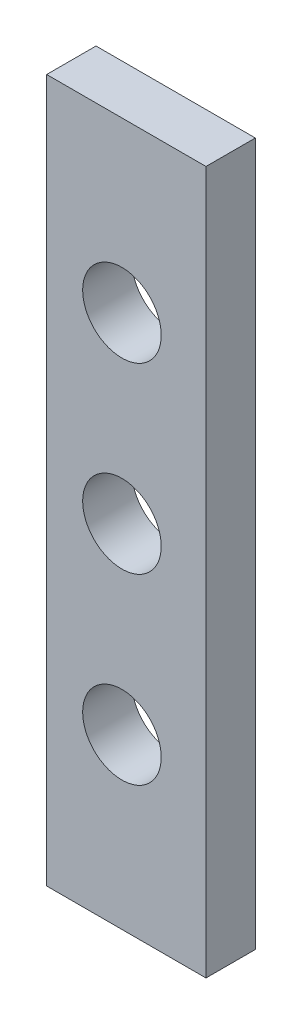
SolidWorks part; units mm, degrees
ref_plane "前视基准面" through (0, 0, 0) normal (0, 0, 1) x (1, 0, 0)
ref_plane "上视基准面" through (0, 0, 0) normal (0, 1, 0) x (1, 0, 0)
ref_plane "右视基准面" through (0, 0, 0) normal (1, 0, 0) x (0, 0, -1)
sketch "草图1" plane through (0, 0, 0) normal (0, 0, 1) x (1, 0, 0)
  line L6 (-130, -105) -> (-121.2816, -105)
  line L7 (-130, -105) -> (-130, -66.5374)
  line L8 (-130, -66.5374) -> (-121.2816, -66.5374)
  line L9 (-121.2816, -105) -> (-121.2816, -66.5374)
extrude "凸台-拉伸1" add sketch "草图1" along normal blind 2.7
hole_wizard "打孔尺寸(%根据十字)槽沉头木螺钉的类型1" positions "草图2" profile "草图3" countersink size "M4" standard "GB"
sketch "草图2" plane through (40.4914, -131.0101, 7) normal (0, 0, 1) x (0, 1, 0)
  point P0 (35.2414, 166.373)
  point P3 (45.2414, 166.373)
  point P6 (55.2414, 166.373)
  point P9 (206.7788, 166.373)
  point P12 (216.7788, 166.373)
  point P15 (226.7788, 166.373)
sketch "草图3" plane through (-125.8816, -95.7687, 7) normal (1, 0, 0) x (0, -1, 0)
  line L0 (0, 0) -> (0, 20.2919)
  line L1 (0, 20.2919) -> (2.15, 19)
  line L2 (2.15, 19) -> (2.15, 1.85)
  line L3 (2.15, 1.85) -> (4, 0)
  line L4 (4, 0) -> (0, 0)
  line L5 (-2.15, 1.85) -> (-4, 0) construction
  line L6 (0, 20.2919) -> (-2.15, 19) construction
  line L7 (0, -6.35) -> (0, 107.95) construction
  dimension "孔直径" = 4.3
  dimension "孔深度" = 19
  dimension "近端锥形沉头孔直径" = 8
  dimension "近端锥形沉头孔角度" = 90
  dimension "导头角度" = 118
